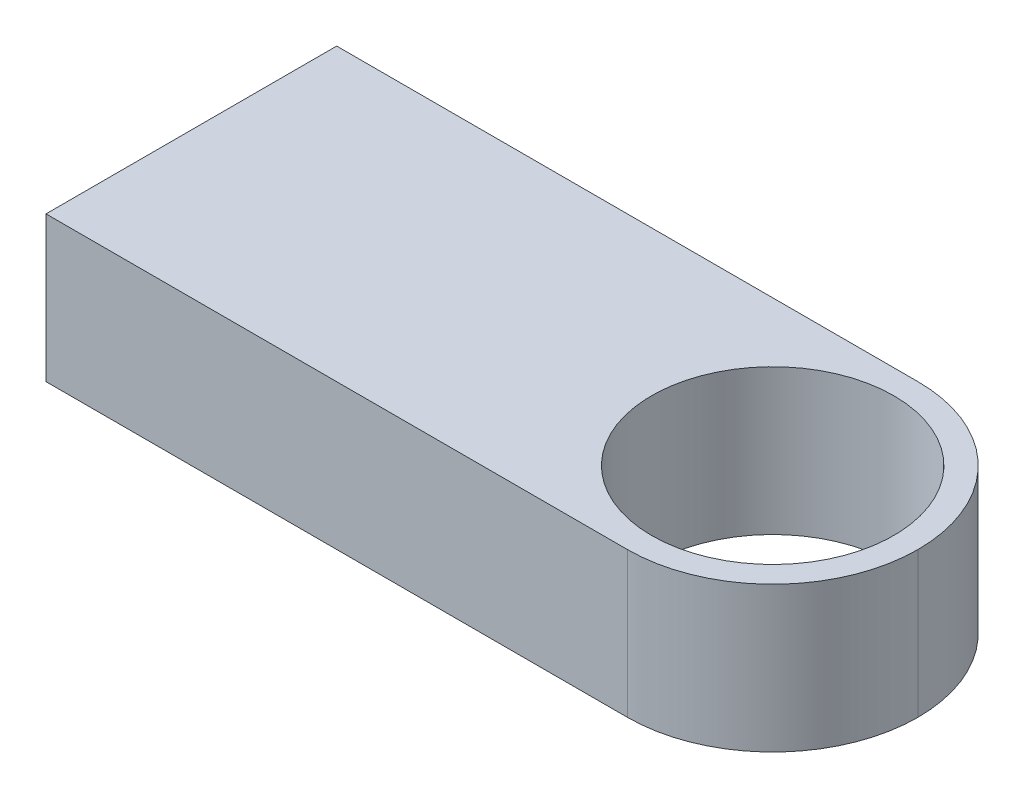
SolidWorks part; units mm, degrees
ref_plane "Front Plane" through (0, 0, 0) normal (0, 0, 1) x (1, 0, 0)
ref_plane "Top Plane" through (0, 0, 0) normal (0, 1, 0) x (1, 0, 0)
ref_plane "Right Plane" through (0, 0, 0) normal (1, 0, 0) x (0, 0, -1)
sketch "Sketch1" plane through (0, 0, 0) normal (1, 0, 0) x (0, 0, -1)
  line L1 (-30, 15) -> (30, 15)
  line L2 (-30, 15) -> (-30, -15)
  line L3 (-30, -15) -> (30, -15)
  line L4 (30, 15) -> (30, -15)
  line L5 (-30, 15) -> (30, -15) construction
  line L6 (-30, -15) -> (30, 15) construction
  point P0 (0, 0)
  dimension "D1" = 60
  dimension "D2" = 30
extrude "Boss-Extrude1" add sketch "Sketch1" along normal blind 150
sketch "Sketch2" plane through (0, 15, 0) normal (0, 1, 0) x (1, 0, 0)
  line L0 (150, 30) -> (150, -30) construction
  line L1 (150, -30) -> (0, -30) construction
  circle A0 centre (120, 0) radius 25
  dimension "D2" = 50
  dimension "D1" = 30
  dimension "D3" = 30
extrude "Cut-Extrude1" cut sketch "Sketch2" against normal up to surface (30 mm away) up to face at (75, -15, 0)
fillet "Fillet1" radius 30 2 edges at (150, 0, -30) (150, 0, 30)
